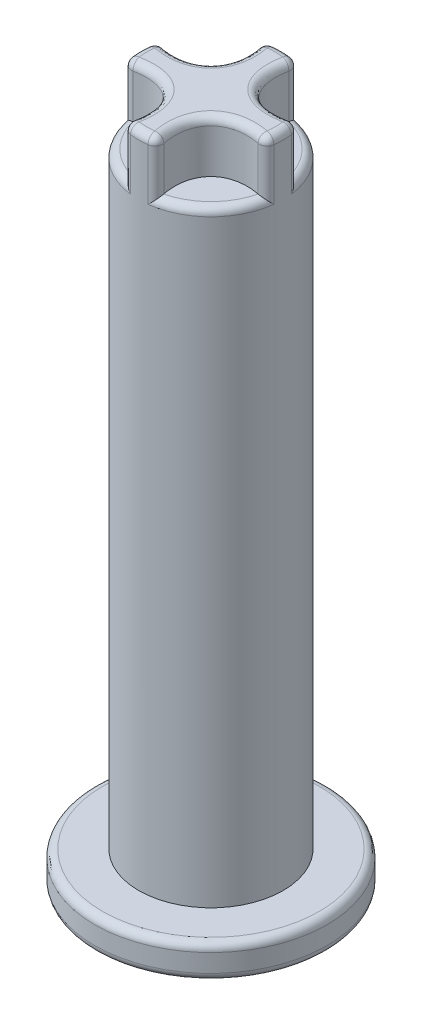
SolidWorks part; units mm, degrees
ref_plane "Front Plane" through (0, 0, 0) normal (0, 0, 1) x (1, 0, 0)
ref_plane "Top Plane" through (0, 0, 0) normal (0, 1, 0) x (1, 0, 0)
ref_plane "Right Plane" through (0, 0, 0) normal (1, 0, 0) x (0, 0, -1)
sketch "Sketch1" plane through (0, 0, 0) normal (0, 1, 0) x (1, 0, 0)
  circle A0 centre (0, 0) radius 2.8
  dimension "D1" = 5.6
extrude "Boss-Extrude1" add sketch "Sketch1" along normal blind 26.8
sketch "Sketch2" plane through (0, 0, 0) normal (0, 1, 0) x (1, 0, 0)
  circle A0 centre (0, 0) radius 4.5
extrude "Boss-Extrude2" add sketch "Sketch2" along normal blind 1.3
sketch "Sketch3" plane through (0, 26.8, 0) normal (0, 1, 0) x (1, 0, 0)
  ellipse E0 centre (-3.4, 3.4) end of major axis (-5.875, 5.875) minor radius 2
  ellipse E1 centre (3.4, 3.4) end of major axis (5.875, 5.875) minor radius 2
  ellipse E2 centre (3.4, -3.4) end of major axis (5.875, -5.875) minor radius 2
  ellipse E3 centre (-3.4, -3.4) end of major axis (-5.875, -5.875) minor radius 2
extrude "Cut-Extrude1" cut sketch "Sketch3" against normal blind 2
fillet "Fillet2" radius 0.3 22 edges at (1.9799, 24.8, -1.9799) (-2.7188, 25.8, -0.6695) (-0.6695, 25.8, -2.7188) (0.6695, 25.8, -2.7188) (2.7188, 25.8, -0.6695) (2.7188, 25.8, 0.6695) (0.6695, 25.8, 2.7188) (-0.6695, 25.8, 2.7188) (-2.7188, 25.8, 0.6695) (2.8, 26.8, 0) (0, 26.8, -2.8) (-2.8, 26.8, 0) (0, 26.8, 2.8) (0.925, 26.8, 0.925) (0.925, 26.8, -0.925) (-0.925, 26.8, -0.925) (-0.925, 26.8, 0.925) (0, 0, 4.5) (0, 1.3, 4.5) (1.9799, 24.8, 1.9799) (-1.9799, 24.8, 1.9799) (-1.9799, 24.8, -1.9799)
